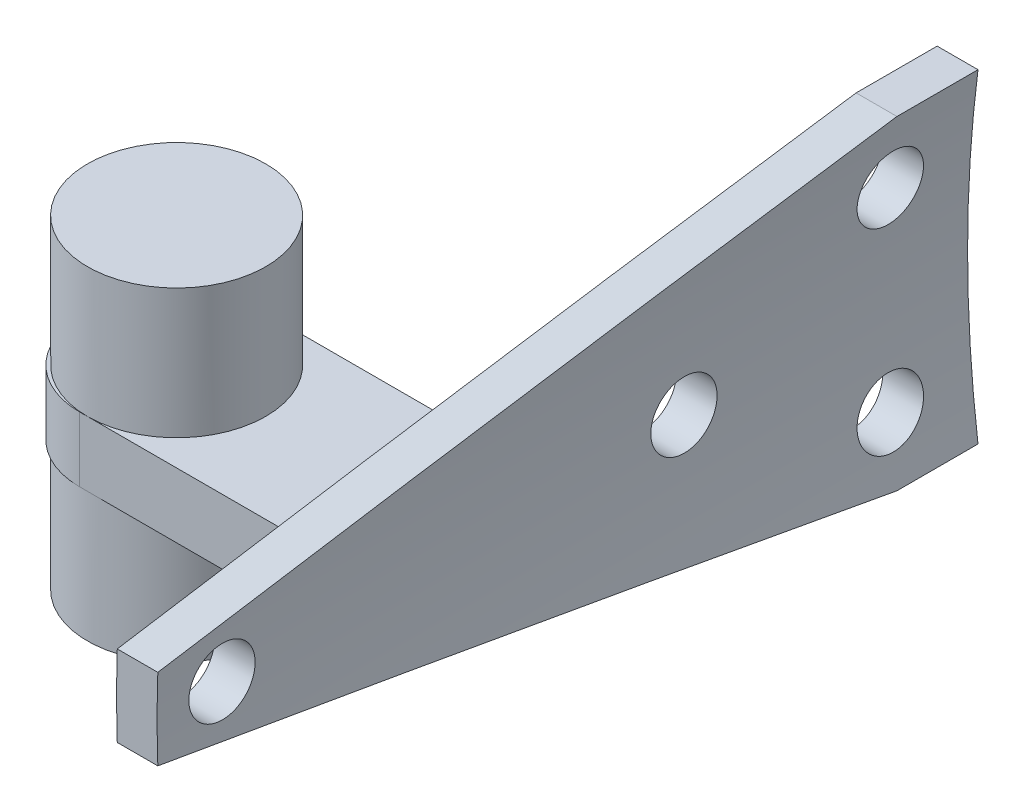
SolidWorks part; units mm, degrees
ref_plane "Front Plane" through (0, 0, 0) normal (0, 0, 1) x (1, 0, 0)
ref_plane "Top Plane" through (0, 0, 0) normal (0, 1, 0) x (1, 0, 0)
ref_plane "Right Plane" through (0, 0, 0) normal (1, 0, 0) x (0, 0, -1)
sketch "Sketch1" plane through (0, 0, 0) normal (0, 0, 1) x (1, 0, 0)
  line L0 (0, 0) -> (-52.4035, 0) construction
  line L1 (-80.078, 10) -> (-77.558, 10)
  line L2 (-80.078, -10) -> (-77.558, -10)
  arc A0 (-77.558, 10) -> (-77.558, -10) centre (0, 0) ccw
  arc A1 (-80.078, 10) -> (-80.078, -10) centre (0, 0) ccw
  dimension "D2" = 78.2
  dimension "D1" = 2.5
  dimension "D3" = 20
extrude "Boss-Extrude1" add sketch "Sketch1" along normal blind 50
sketch "Sketch2" plane through (0, 0, 0) normal (1, 0, 0) x (0, 0, -1)
  line L0 (0, 10) -> (0, -10)
  line L1 (0, 10) -> (-50, 10) construction
  line L2 (0, 10) -> (0, -10) construction
  line L3 (0, -10) -> (-50, -10) construction
  line L4 (-50, 10) -> (-50, -10) construction
  line L5 (0, -10) -> (-5, -10)
  line L6 (-5, -10) -> (-50, -2.5)
  line L7 (-50, -2.5) -> (-50, 2.5)
  line L8 (-50, 2.5) -> (-5, 10)
  line L9 (-5, 10) -> (0, 10)
  line L10 (0, 0) -> (-50.031, 0) construction
  line L12 (-88.7937, 27.6855) -> (20.3533, 27.6855)
  line L13 (-88.7937, 27.6855) -> (-88.7937, -33.0502)
  line L14 (-88.7937, -33.0502) -> (20.3533, -33.0502)
  line L15 (20.3533, 27.6855) -> (20.3533, -33.0502)
  dimension "D1" = 5
extrude "Cut-Extrude1" cut sketch "Sketch2" against normal through all
hole_wizard "#20 (0.161) Diameter Hole1" positions "Sketch5" profile "Sketch4" hole size "#20" standard "ANSI Inch" end condition through all
sketch "Sketch5" plane through (0, 0, 0) normal (1, 0, 0) x (0, 0, -1)
  line L1 (0, -10) -> (-42.3856, -10)
  line L2 (0, -10) -> (0, 10)
  line L3 (0, 10) -> (-42.3856, 10)
  line L4 (-42.3856, -10) -> (-42.3856, 10)
  line L7 (-5, 10) -> (0, 10) construction
  line L8 (0, 0) -> (-42.3856, 0)
  line L10 (-5, 6) -> (-5, -6)
  line L11 (-50, 2.5) -> (-50, -2.5) construction
  point P0 (-46, 0)
  point P164 (-5, 6)
  point P165 (-5, -6)
  point P172 (-5, 0)
  point P177 (-17.5, 0)
  dimension "D1" = 5
  dimension "D2" = 4
  dimension "D3" = 4
  dimension "D4" = 12.5
sketch "Sketch4" plane through (0, 0, 46) normal (0, 1, 0) x (0, 0, -1)
  line L0 (0, 0) -> (0, 80.7)
  line L1 (0, 80.7) -> (2.0447, 80.7)
  line L2 (2.0447, 80.7) -> (2.0447, 0)
  line L5 (2.0447, 0) -> (0, 0)
  line L11 (0, -6.35) -> (0, 107.95) construction
  dimension "Thru Hole Dia." = 4.0894
  dimension "Thru Hole Depth" = 80.7
ref_plane "Plane1" through (-80, 0, 0) normal (1, 0, 0) x (0, 0, -1)
sketch "Sketch7" plane through (-80, 0, -87.9998) normal (1, 0, 0) x (0, 0, -1)
  line L0 (-87.9998, 0) -> (-80.3469, 0) construction
  line L1 (-125.9998, 2) -> (-114.9998, 2)
  line L2 (-125.9998, 2) -> (-125.9998, -2)
  line L3 (-125.9998, -2) -> (-114.9998, -2)
  line L4 (-114.9998, 2) -> (-114.9998, -2)
  line L5 (-87.9998, 10) -> (-87.9998, -10) construction
  line L6 (-87.9998, -10) -> (-87.9998, 10) construction
  circle A2 centre (-133.9998, 0) radius 2.0447 construction
  point P8 (-125.9998, 0)
  dimension "D2" = 11
  dimension "D1" = 4
  dimension "D3" = 8
extrude "Boss-Extrude2" add sketch "Sketch7" against normal blind 20
fillet "Fillet1" radius 2 4 edges at (-80.6752, 2, 32.5) (-80.7, 0, 38) (-80.7, 0, 27) (-80.6752, -2, 32.5)
sketch "Sketch8" plane through (0, -2, 0) normal (0, -1, 0) x (1, 0, 0)
  line L1 (-89, 27) -> (-100, 27) construction
  line L2 (-89, 27) -> (-89, 38) construction
  line L3 (-89, 38) -> (-100, 38) construction
  line L4 (-100, 27) -> (-100, 38) construction
  line L5 (-89, 27) -> (-100, 38) construction
  line L6 (-89, 38) -> (-100, 27) construction
  circle A0 centre (-94.5, 32.5) radius 5.5
  point P0 (-94.5, 32.5)
extrude "Boss-Extrude3" add sketch "Sketch8" along normal blind 8 and the other way blind 12
fillet "Fillet2" radius 5 2 edges at (-100, 0, 38) (-100, 0, 27)
equation "\"TubeDiameter\" = 6.000in"
equation "\"D2@Sketch1\"=\"TubeDiameter\"/2+2mm"
